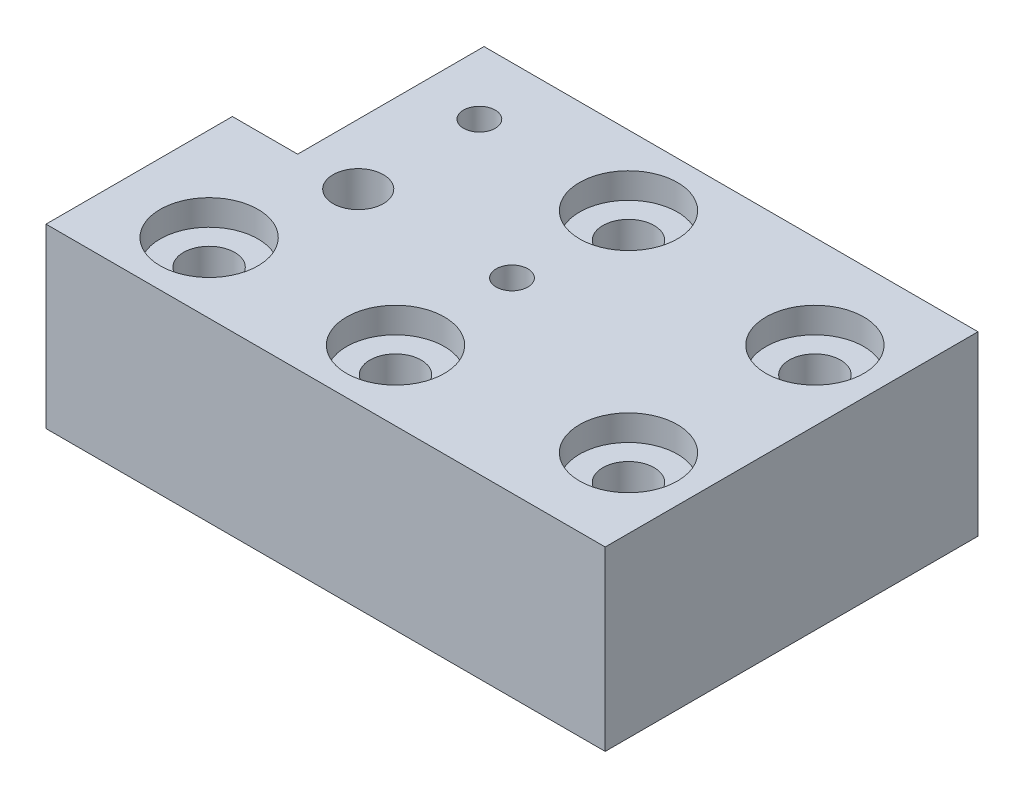
SolidWorks part; units mm, degrees
ref_plane "Front Plane" through (0, 0, 0) normal (0, 0, 1) x (1, 0, 0)
ref_plane "Top Plane" through (0, 0, 0) normal (0, 1, 0) x (1, 0, 0)
ref_plane "Right Plane" through (0, 0, 0) normal (1, 0, 0) x (0, 0, -1)
sketch "Sketch1" plane through (0, 0, 0) normal (0, 1, 0) x (1, 0, 0)
  line L0 (20, 30) -> (60, 30) construction
  line L1 (0, 0) -> (60, 0)
  line L2 (0, 0) -> (0, 20)
  line L4 (60, 0) -> (60, 40)
  line L5 (0, 10) -> (60, 10) construction
  line L6 (50, 0) -> (50, 40) construction
  line L7 (10, 0) -> (10, 20) construction
  line L8 (30, 0) -> (30, 40) construction
  line L9 (20, 40) -> (20, 0) construction
  line L10 (60, 20) -> (0, 20) construction
  line L11 (40, 40) -> (40, 0) construction
  line L12 (20, 40) -> (60, 40)
  line L13 (0, 20) -> (20, 20)
  line L14 (20, 20) -> (20, 40)
  dimension "D2" = 40
  dimension "D3" = 20
  dimension "D5" = 10
  dimension "D6" = 20
  dimension "D7" = 20
  dimension "D8" = 10
  dimension "D9" = 10
extrude "Boss-Extrude1" add sketch "Sketch1" along normal blind 10
sketch "Sketch2" plane through (0, 10, 0) normal (0, 1, 0) x (1, 0, 0)
  line L0 (13.5, 40) -> (13.5, 20) construction
  line L1 (20, 40) -> (7, 40)
  line L4 (7, 40) -> (7, 20)
  line L5 (20, 20) -> (0, 20) construction
  line L6 (0, 20) -> (0, 0)
  line L7 (0, 0) -> (60, 0)
  line L8 (60, 0) -> (60, 40)
  line L9 (60, 40) -> (20, 40)
  line L10 (20, 40) -> (20, 20)
  line L11 (20, 20) -> (0, 20)
  line L12 (0, 20) -> (0, 0)
  line L13 (0, 0) -> (60, 0)
  line L14 (60, 0) -> (60, 40)
  line L15 (60, 40) -> (20, 40)
  line L17 (7, 20) -> (0, 20)
  line L20 (30, 0) -> (30, 40) construction
  point P12 (13.5, 33)
  point P13 (13.5, 20)
  point P14 (30, 20)
  dimension "D2" = 13
  dimension "D3" = 7
  dimension "D4" = 13
  dimension "D1" = 0
extrude "Boss-Extrude2" add sketch "Sketch2" along normal blind 9
hole_wizard "CBORE for M5 SBHCS1" positions "Sketch3" profile "Sketch4" counterbore size "M5" standard "ANSI Metric" end condition through all
sketch "Sketch3" plane through (0, 19, 0) normal (0, 1, 0) x (1, 0, 0)
  line L0 (10, 0) -> (10, 20) construction
  line L1 (30, 0) -> (30, 40) construction
  line L4 (0, 0) -> (60, 0) construction
  line L5 (20, 40) -> (60, 40) construction
  point P0 (10, 7.5)
  point P4 (30, 7.5)
  point P16 (30, 32.5)
  point P20 (0, 0)
  point P21 (0, 0)
  point P24 (0, 0)
  point P25 (30, 33.6169)
  dimension "D1" = 7.5
  dimension "D2" = 7.5
sketch "Sketch4" plane through (10, 19, -7.5) normal (1, 0, 0) x (0, 0, 1)
  line L0 (0, 0) -> (0, 19)
  line L1 (0, 19) -> (2.75, 19)
  line L3 (2.75, 19) -> (2.75, 2.75)
  line L4 (2.75, 2.75) -> (5.25, 2.75)
  line L5 (5.25, 2.75) -> (5.25, 0)
  line L7 (5.25, 0) -> (0, 0)
  line L11 (0, -6.35) -> (0, 107.95) construction
  dimension "Thru Hole Dia." = 5.5
  dimension "Thru Hole Depth" = 19
  dimension "C'Bore Dia." = 10.5
  dimension "C'Bore Depth" = 2.75
hole_wizard "CBORE for M5 SBHCS2" positions "Sketch5" profile "Sketch6" counterbore size "M5" standard "ANSI Metric" end condition through all
sketch "Sketch5" plane through (0, 19, 0) normal (0, 1, 0) x (1, 0, 0)
  line L0 (20, 30) -> (60, 30) construction
  line L1 (0, 10) -> (60, 10) construction
  line L2 (60, 0) -> (60, 40) construction
  point P0 (52.5, 30)
  point P4 (52.5, 10)
  point P11 (0, 0)
  dimension "D1" = 7.5
sketch "Sketch6" plane through (52.5, 19, -30) normal (1, 0, 0) x (0, 0, 1)
  line L0 (0, 0) -> (0, 19)
  line L1 (0, 19) -> (2.75, 19)
  line L3 (2.75, 19) -> (2.75, 2.75)
  line L4 (2.75, 2.75) -> (5.25, 2.75)
  line L5 (5.25, 2.75) -> (5.25, 0)
  line L7 (5.25, 0) -> (0, 0)
  line L11 (0, -6.35) -> (0, 107.95) construction
  dimension "Thru Hole Dia." = 5.5
  dimension "Thru Hole Depth" = 19
  dimension "C'Bore Dia." = 10.5
  dimension "C'Bore Depth" = 2.75
hole_wizard "CBORE for M3 SBHCS1" positions "Sketch9" profile "Sketch10" counterbore size "M3" standard "ANSI Metric" end condition through all
sketch "Sketch9" plane through (0, 0, 0) normal (0, -1, 0) x (-1, 0, 0)
  line L0 (-30, 0) -> (-30, 40) construction
  point P0 (-30, 20)
sketch "Sketch10" plane through (30, 0, -20) normal (1, 0, 0) x (0, 0, -1)
  line L0 (0, 0) -> (0, 19)
  line L1 (0, 19) -> (1.7, 19)
  line L3 (1.7, 19) -> (1.7, 16)
  line L4 (1.7, 16) -> (3.35, 16)
  line L5 (3.35, 16) -> (3.35, 0)
  line L7 (3.35, 0) -> (0, 0)
  line L11 (0, -6.35) -> (0, 107.95) construction
  dimension "Thru Hole Dia." = 3.4
  dimension "Thru Hole Depth" = 19
  dimension "C'Bore Dia." = 6.7
  dimension "C'Bore Depth" = 16
hole_wizard "CBORE for M3 SBHCS2" positions "Sketch11" profile "Sketch12" counterbore size "M3" standard "ANSI Metric" end condition through all
sketch "Sketch11" plane through (0, 10, 0) normal (0, -1, 0) x (-1, 0, 0)
  point P0 (-13.5, 33)
sketch "Sketch12" plane through (13.5, 10, -33) normal (1, 0, 0) x (0, 0, -1)
  line L0 (0, 0) -> (0, 9)
  line L1 (0, 9) -> (1.7, 9)
  line L3 (1.7, 9) -> (1.7, 6)
  line L4 (1.7, 6) -> (3.35, 6)
  line L5 (3.35, 6) -> (3.35, 0)
  line L7 (3.35, 0) -> (0, 0)
  line L11 (0, -6.35) -> (0, 107.95) construction
  dimension "Thru Hole Dia." = 3.4
  dimension "Thru Hole Depth" = 9
  dimension "C'Bore Dia." = 6.7
  dimension "C'Bore Depth" = 6
hole_wizard "Ø5.4 (5.4) Diameter Hole1" positions "Sketch13" profile "Sketch14" hole size "Ø5.4" standard "ANSI Metric" end condition through all
sketch "Sketch13" plane through (0, 0, 0) normal (0, -1, 0) x (-1, 0, 0)
  point P0 (-13.5, 20)
  point P5 (0, 0)
  point P6 (-13.5156, 19.8588)
sketch "Sketch14" plane through (13.5, 0, -20) normal (1, 0, 0) x (0, 0, -1)
  line L0 (0, 0) -> (0, 19)
  line L1 (0, 19) -> (2.7, 19)
  line L2 (2.7, 19) -> (2.7, 0)
  line L5 (2.7, 0) -> (0, 0)
  line L11 (0, -6.35) -> (0, 107.95) construction
  dimension "Thru Hole Dia." = 5.4
  dimension "Thru Hole Depth" = 19
fillet "Fillet3" radius 9 2 edges at (20, 10, -30) (8.9, 10, -20)
